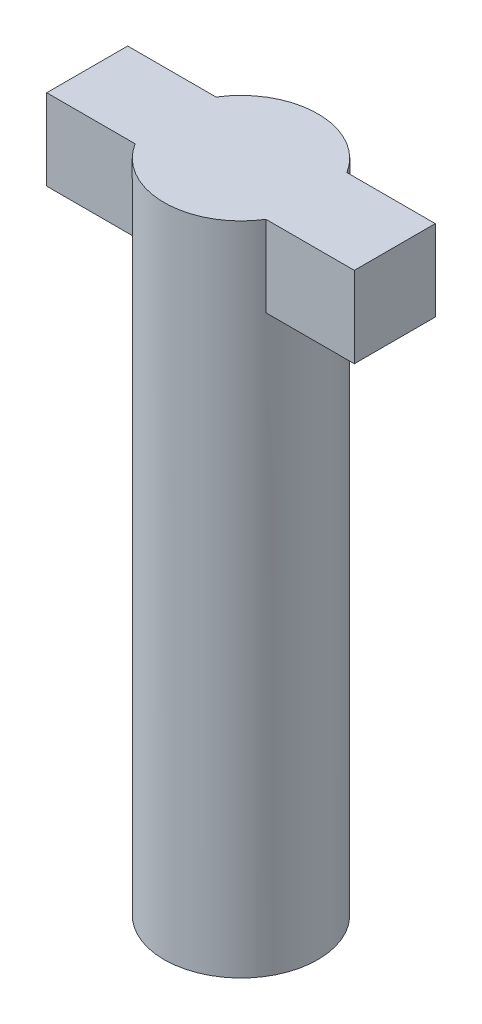
SolidWorks part; units mm, degrees
ref_plane "Front Plane" through (0, 0, 0) normal (0, 0, 1) x (1, 0, 0)
ref_plane "Top Plane" through (0, 0, 0) normal (0, 1, 0) x (1, 0, 0)
ref_plane "Right Plane" through (0, 0, 0) normal (1, 0, 0) x (0, 0, -1)
sketch "Sketch1" plane through (0, 0, 0) normal (0, 1, 0) x (1, 0, 0)
  circle A0 centre (0, 0) radius 0.95
  dimension "D1" = 1.9
extrude "Body" add sketch "Sketch1" along normal blind 8.1
sketch "Sketch2" plane through (0, 8.1, 0) normal (0, 1, 0) x (1, 0, 0)
  line L0 (0, 0) -> (-1.9, 0) construction
  line L1 (0, 0.5) -> (-1.9, 0.5)
  line L2 (0, -0.5) -> (-1.9, -0.5)
  line L3 (-1.9, 0.5) -> (-1.9, -0.5)
  line L4 (0, 0) -> (0, 0.2952) construction
  line L5 (0, 0) -> (1.9, 0) construction
  line L6 (0, -0.5) -> (1.9, -0.5)
  line L7 (1.9, 0.5) -> (1.9, -0.5)
  line L8 (0, 0.5) -> (1.9, 0.5)
  circle A0 centre (0, 0) radius 0.95 construction
  circle A1 centre (0, 0) radius 0.95
  circle M6 centre (0, 0) radius 0.95
  dimension "D1" = 1.9
  dimension "D2" = 0.5
  dimension "D3" = 0.5
extrude "Lock" add sketch "Sketch2" against normal blind 1 contours L1 L3 L2 M6 | L8 L6 L7 M6 region at (-1.4012, 8.1, 0) region at (1.4012, 8.1, 0)
equation "\"BoltD\"=2mm"
equation "\"NutShortSide\"=4mm"
equation "\"NutLongSide\"=4.5mm"
equation "\"SmallScrewD\"=1.2mm"
equation "\"SmallScrewHatD\"=2mm"
equation "\"TubeOuterD\"=1.2mm"
equation "\"BasicPulleyD\"=15mm"
equation "\"GrooveDepth\"=0.7mm"
equation "\"Cable1D\"=0.4mm"
equation "\"Cable2D\"=0.3mm"
equation "\"BallBearingInnerD\"=2mm"
equation "\"BallBearingOuterD\"=4mm"
equation "\"D1@Sketch1\"=\"BallBearingInnerD\"-0.1"
equation "\"BoltHatD\"=3.2mm"
equation "\"BallBearingThickness\"=2mm"
equation "\"HumerusL\"=37.2mm"
equation "\"HumerusElbowSidePulleyD\"=10mm"
equation "\"RadiusL\"=68.1mm"
equation "\"Finger1L\"=120mm"
equation "\"Finger2L\"=100mm"
equation "\"Finger3L\"=80mm"
equation "\"ElbowExtendedAngle\"=140deg"
equation "\"ElbowFlexedAngle\"=38deg"
equation "\"BearingCapD\"=12mm"
equation "\"TubeClipW\"=1.5mm"
equation "\"TubeClipH\"=1mm"
equation "\"TubeClipLock_SideL\"=1.6mm"
equation "\"TubeClipLock_W\"=0.7mm"
equation "\"Digit5ExtendedAngle\"=80deg"
equation "\"Digit5FlexedAngle\"=24deg"
equation "\"Digit4ExtendedAngle\"=108deg"
equation "\"Digit4FlexedAngle\"=34deg"
equation "\"Digit3ExtendedAngle\"=145deg"
equation "\"Digit3FlexedAngle\"=44deg"
